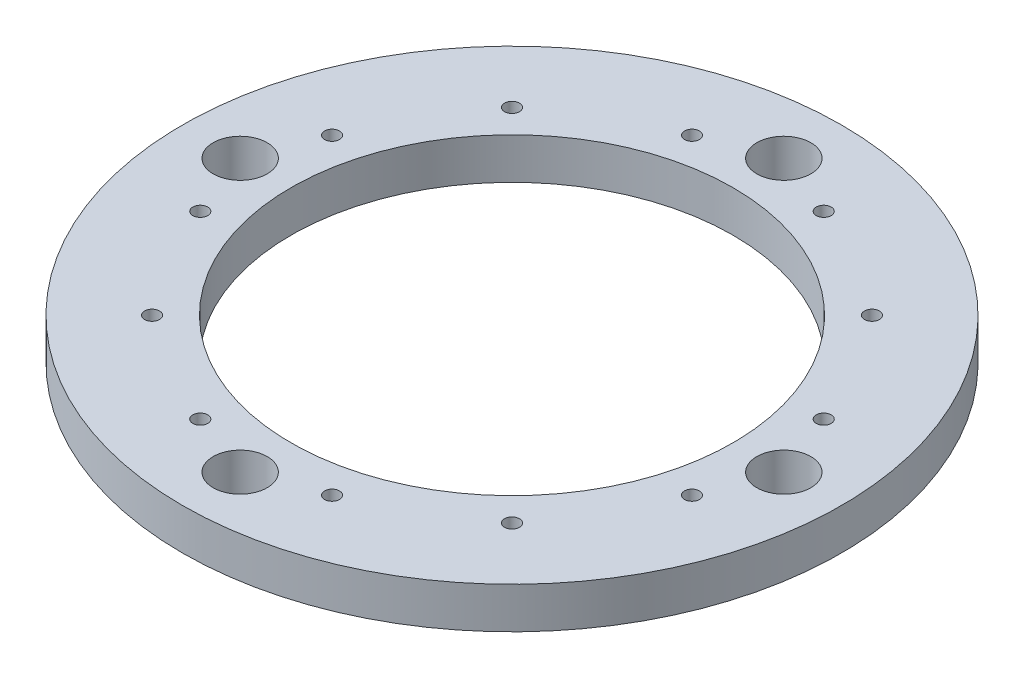
SolidWorks part; units mm, degrees
material "6061 Alloy"
ref_plane "Front Plane" through (0, 0, 0) normal (0, 0, 1) x (1, 0, 0)
ref_plane "Top Plane" through (0, 0, 0) normal (0, 1, 0) x (1, 0, 0)
ref_plane "Right Plane" through (0, 0, 0) normal (1, 0, 0) x (0, 0, -1)
sketch "Centering Ring Profile" plane through (0, 0, 0) normal (0, 1, 0) x (1, 0, 0)
  circle A0 centre (0, 0) radius 51.1048
  circle A1 centre (0, 0) radius 76.2
  dimension "D1" = 102.2096
  dimension "D2" = 152.4
extrude "Centering Ring Body" add sketch "Centering Ring Profile" along normal blind 9.525
sketch "Motor Mount Hole Profile" plane through (0, 9.525, 0) normal (0, 1, 0) x (1, 0, 0)
  line L0 (-15.2315, 56.8447) -> (0, 0) construction
  line L1 (0, 0) -> (0, 76.2) construction
  circle A0 centre (-15.2315, 56.8447) radius 1.7272
  circle A1 centre (0, 0) radius 76.2 construction
  circle A2 centre (15.2315, 56.8447) radius 1.7272
  circle A3 centre (41.6132, 41.6132) radius 1.7272
  circle A4 centre (56.8447, 15.2315) radius 1.7272
  circle A5 centre (56.8447, -15.2315) radius 1.7272
  circle A6 centre (41.6132, -41.6132) radius 1.7272
  circle A7 centre (15.2315, -56.8447) radius 1.7272
  circle A8 centre (-15.2315, -56.8447) radius 1.7272
  circle A9 centre (-41.6132, -41.6132) radius 1.7272
  circle A10 centre (-56.8447, -15.2315) radius 1.7272
  circle A11 centre (-56.8447, 15.2315) radius 1.7272
  circle A12 centre (-41.6132, 41.6132) radius 1.7272
  point P33 (0, 0)
  dimension "D1" = 15
  dimension "D2" = 3.4544
  dimension "D3" = 58.85
  dimension "D4" = 12
extrude "Motor Mount Hole Cuts" cut sketch "Motor Mount Hole Profile" against normal through all
sketch "Vent Hole Profile" plane through (0, 9.525, 0) normal (0, 1, 0) x (1, 0, 0)
  line L0 (-62.85, 0) -> (0, 0) construction
  circle A0 centre (-62.85, 0) radius 6.25
  circle A1 centre (0, 62.85) radius 6.25
  circle A2 centre (62.85, 0) radius 6.25
  circle A3 centre (0, -62.85) radius 6.25
  point P13 (0, 0)
  dimension "D1" = 12.5
  dimension "D2" = 62.85
  dimension "D3" = 4
extrude "Vent Hole Cuts" cut sketch "Vent Hole Profile" against normal through all
equation "\"Ring Thickness\"= 0.375"
equation "\"Outer Diameter\"= 6"
equation "\"Inner Diameter\"= 4.024"
equation "\"D1@Centering Ring Profile\"=\"Inner Diameter\""
equation "\"D2@Centering Ring Profile\"=\"Outer Diameter\""
equation "\"D1@Centering Ring Body\"=\"Ring Thickness\""
